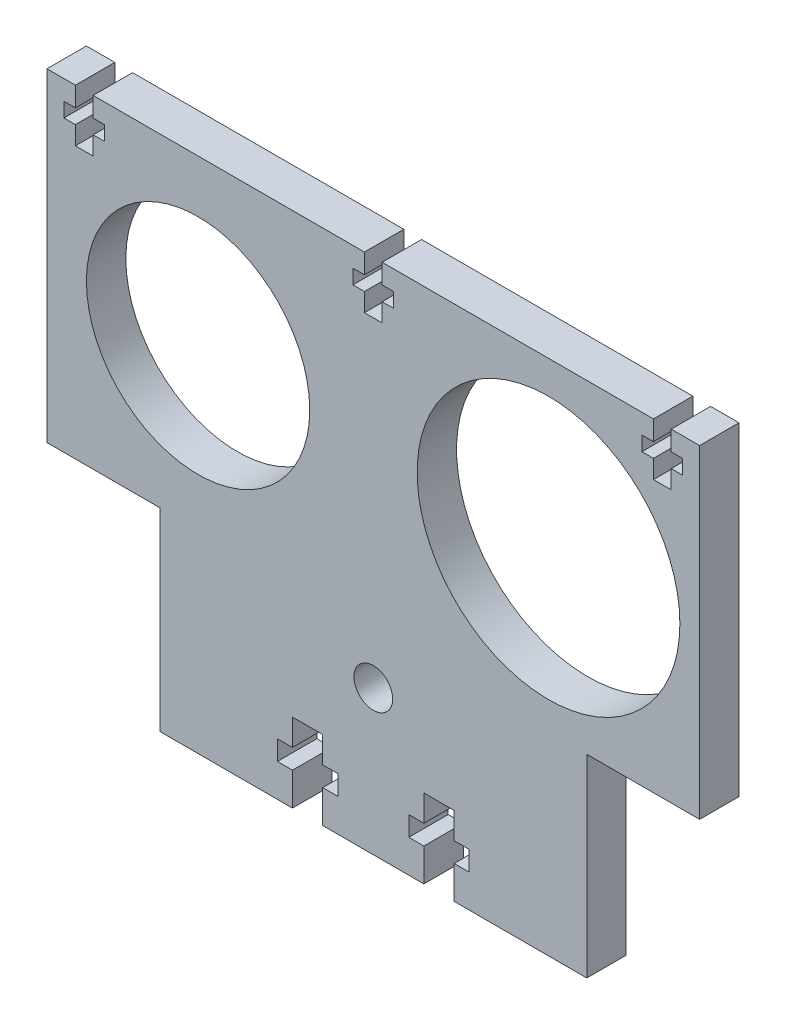
SolidWorks part; units mm, degrees
material "ABS"
ref_plane "Front Plane" through (0, 0, 0) normal (0, 0, 1) x (1, 0, 0)
ref_plane "Top Plane" through (0, 0, 0) normal (0, 1, 0) x (1, 0, 0)
ref_plane "Right Plane" through (0, 0, 0) normal (1, 0, 0) x (0, 0, -1)
sketch "Sketch1" plane through (0, 0, 0) normal (0, 0, 1) x (1, 0, 0)
  line L0 (0, 0) -> (-26.6757, 31.7908) construction
  line L1 (0, 0) -> (0, 56.7908) construction
  line L2 (-32.5, 7.5) -> (-32.5, -22)
  line L3 (-32.5, -22) -> (32.5, -22)
  line L4 (32.5, 7.5) -> (49.6757, 7.5)
  line L5 (0, 0) -> (0, -22) construction
  line L6 (49.6757, 7.5) -> (49.6757, 56.7908)
  line L7 (0, 0) -> (26.6757, 31.7908) construction
  line L10 (-32.5, 7.5) -> (-49.6757, 7.5)
  line L11 (-49.6757, 7.5) -> (-49.6757, 56.7908)
  line L12 (-49.6757, 56.7908) -> (49.6757, 56.7908)
  line L13 (32.5, 7.5) -> (32.5, -22)
  circle A0 centre (0, 0) radius 2.95
  circle A1 centre (-26.6757, 31.7908) radius 17
  circle A2 centre (26.6757, 31.7908) radius 20
  point P16 (0, 56.7908)
  dimension "D1" = 5.9
  dimension "D9" = 34
  dimension "D10" = 40
  dimension "D2" = 41.5
  dimension "D4" = 40
  dimension "D5" = 22
  dimension "D6" = 65
  dimension "D7" = 29.5
  dimension "D8" = 23
  dimension "D3" = 25
  dimension "D11" = 40
extrude "Boss-Extrude1" add sketch "Sketch1" along normal blind 6
sketch "Sketch3" plane through (0, 0, 6) normal (0, 0, 1) x (1, 0, 0)
  line L0 (-32.5, -22) -> (32.5, -22) construction
  line L1 (-12.3, -22) -> (-7.7, -22)
  line L2 (-12.3, -22) -> (-12.3, -17)
  line L3 (-12.3, -10) -> (-7.7, -10)
  line L4 (-7.7, -22) -> (-7.7, -17)
  line L5 (0, 0) -> (0, -22) construction
  line L6 (-7.7, -14) -> (-5.4, -14)
  line L7 (-14.6, -14) -> (-12.3, -14)
  line L8 (-14.6, -14) -> (-14.6, -17)
  line L9 (-14.6, -17) -> (-12.3, -17)
  line L10 (-5.4, -14) -> (-5.4, -17)
  line L11 (-12.3, -14) -> (-12.3, -10)
  line L12 (-7.7, -17) -> (-5.4, -17)
  line L13 (-7.7, -14) -> (-7.7, -10)
  line L14 (7.7, -14) -> (7.7, -10)
  line L15 (7.7, -17) -> (5.4, -17)
  line L16 (12.3, -14) -> (12.3, -10)
  line L17 (5.4, -14) -> (5.4, -17)
  line L18 (14.6, -17) -> (12.3, -17)
  line L19 (14.6, -14) -> (14.6, -17)
  line L20 (14.6, -14) -> (12.3, -14)
  line L21 (7.7, -14) -> (5.4, -14)
  line L22 (7.7, -22) -> (7.7, -17)
  line L23 (12.3, -10) -> (7.7, -10)
  line L24 (12.3, -22) -> (12.3, -17)
  line L25 (12.3, -22) -> (7.7, -22)
  point P6 (-10, -10)
  point P18 (-13.45, -17)
  dimension "D1" = 4.6
  dimension "D2" = 10
  dimension "D3" = 12
  dimension "D4" = 9.2
  dimension "D5" = 3
  dimension "D6" = 5
extrude "Cut-Extrude2" cut sketch "Sketch3" against normal through all
sketch "Sketch4" plane through (0, 0, 6) normal (0, 0, 1) x (1, 0, 0)
  line L0 (42.65, 56.7908) -> (42.65, 53.7908)
  line L1 (49.6757, 56.7908) -> (-49.6757, 56.7908) construction
  line L2 (42.65, 53.7908) -> (40.9, 53.7908)
  line L3 (40.9, 53.7908) -> (40.9, 51.5908)
  line L4 (40.9, 51.5908) -> (42.65, 51.5908)
  line L5 (42.65, 51.5908) -> (42.65, 48.7908)
  line L6 (42.65, 48.7908) -> (45.35, 48.7908)
  line L7 (45.35, 48.7908) -> (45.35, 51.5908)
  line L8 (45.35, 51.5908) -> (47.1, 51.5908)
  line L9 (47.1, 51.5908) -> (47.1, 53.7908)
  line L10 (47.1, 53.7908) -> (45.35, 53.7908)
  line L11 (45.35, 53.7908) -> (45.35, 56.7908)
  line L12 (45.35, 56.7908) -> (42.65, 56.7908)
  line L13 (0, 0) -> (0, 56.7908) construction
  line L14 (-45.35, 56.7908) -> (-42.65, 56.7908)
  line L15 (-45.35, 53.7908) -> (-45.35, 56.7908)
  line L16 (-47.1, 53.7908) -> (-45.35, 53.7908)
  line L17 (-47.1, 51.5908) -> (-47.1, 53.7908)
  line L18 (-45.35, 51.5908) -> (-47.1, 51.5908)
  line L19 (-45.35, 48.7908) -> (-45.35, 51.5908)
  line L20 (-42.65, 48.7908) -> (-45.35, 48.7908)
  line L21 (-42.65, 51.5908) -> (-42.65, 48.7908)
  line L22 (-40.9, 51.5908) -> (-42.65, 51.5908)
  line L23 (-40.9, 53.7908) -> (-40.9, 51.5908)
  line L24 (-42.65, 53.7908) -> (-40.9, 53.7908)
  line L25 (-42.65, 56.7908) -> (-42.65, 53.7908)
  line L26 (-1.35, 56.7908) -> (1.35, 56.7908)
  line L27 (1.35, 56.7908) -> (1.35, 53.7908)
  line L28 (1.35, 53.7908) -> (3.1, 53.7908)
  line L29 (3.1, 53.7908) -> (3.1, 51.5908)
  line L30 (3.1, 51.5908) -> (1.35, 51.5908)
  line L31 (1.35, 51.5908) -> (1.35, 48.7908)
  line L32 (1.35, 48.7908) -> (-1.35, 48.7908)
  line L33 (-1.35, 48.7908) -> (-1.35, 51.5908)
  line L34 (-1.35, 51.5908) -> (-3.1, 51.5908)
  line L35 (-3.1, 51.5908) -> (-3.1, 53.7908)
  line L36 (-3.1, 53.7908) -> (-1.35, 53.7908)
  line L37 (-1.35, 53.7908) -> (-1.35, 56.7908)
  point P18 (44, 48.7908)
  point P46 (0, 48.7908)
  dimension "D1" = 2.7
  dimension "D2" = 2.2
  dimension "D3" = 6.2
  dimension "D4" = 3
  dimension "D5" = 8
  dimension "D6" = 44
extrude "Cut-Extrude3" cut sketch "Sketch4" against normal through all
equation "\"smallPulleyTeeth\"= 15"
equation "\"largePulleyTeeth\"= 30"
equation "\"eighthThick\"= 3.0mm"
equation "\"sixteenthThick\"= 1.7mm"
equation "\"quarterThick\"=6.0mm"
equation "\"OD\"= 145mm"
equation "\"puckAngle\"= 60.5deg"
equation "\"puckDiam\"= 76.5mm"
equation "\"axlePress\"= 5.9mm"
equation "\"D1@Sketch1\"=\"axlePress\""
equation "\"D1@Boss-Extrude1\"=\"quarterThick\""
equation "\"press\"= 0.2mm"
equation "\"wheelClear\"= 0.3mm"
equation "\"10-32clear\"= 4.8mm"
equation "\"D1@Sketch3\"=\"10-32clear\" - \"press\""
equation "\"6-32clear\"= 3.3mm"
equation "\"8-32clear\"= 4.0mm"
equation "\"wheelHeight\"= 22mm"
equation "\"D5@Sketch1\"=\"wheelHeight\""
equation "\"4-40clear\"= 3.0mm"
equation "\"wheelWell\"= 65mm"
equation "\"D6@Sketch1\"=\"wheelWell\""
equation "\"D7@Sketch1\"=\"eighthThick\"*10 - 0.5"
equation "\"puckDist\"= 85mm"
equation "\"scoopFillet\"= 5mm"
equation "\"10-32tap\"= 4.45mm"
equation "\"ledSmall\"= 3.1mm"
equation "\"ledLarge\"= 4.2mm"
equation "\"ledLength\"= 4.2mm"
equation "\"4-40close\"= 2.7mm"
equation "\"4-40nutThick\"= 2.2mm"
equation "\"4-40nutWidth\"= 6.2mm"
equation "\"D3@Sketch4\"=\"4-40nutWidth\""
equation "\"D2@Sketch4\"=\"4-40nutThick\""
equation "\"D1@Sketch4\"=\"4-40close\""
